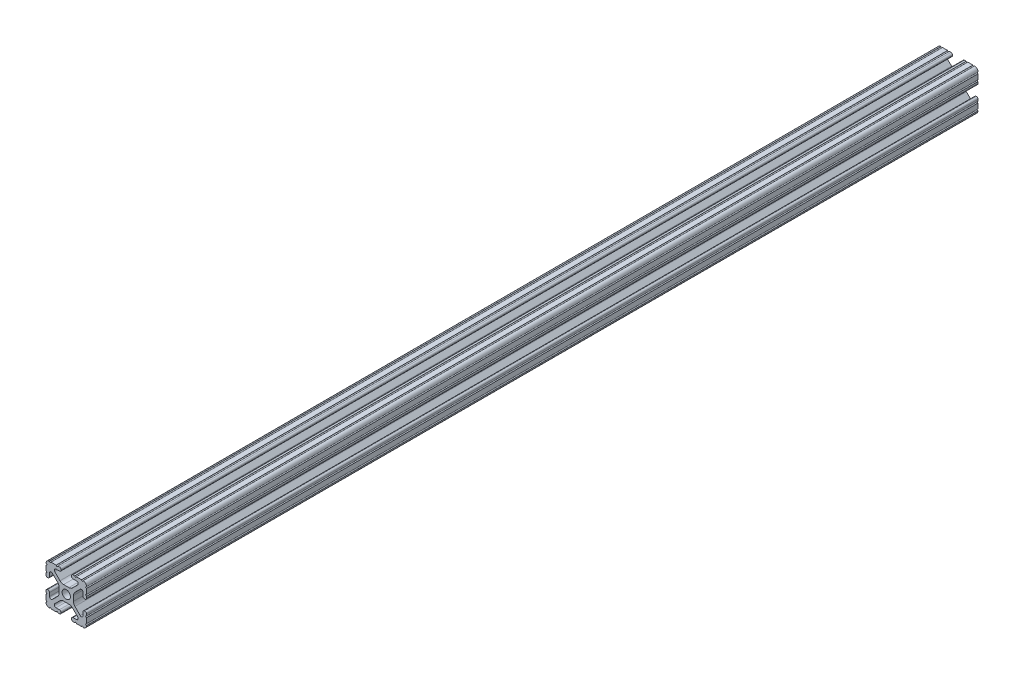
SolidWorks part; units mm, degrees
ref_plane "Front Plane" through (0, 0, 0) normal (0, 0, 1) x (1, 0, 0)
ref_plane "Top Plane" through (0, 0, 0) normal (0, 1, 0) x (1, 0, 0)
ref_plane "Right Plane" through (0, 0, 0) normal (1, 0, 0) x (0, 0, -1)
sketch "Sketch1" plane through (0, 0, 0) normal (0, 0, 1) x (1, 0, 0)
  line L88 (-7.1797, -8.6452) -> (-3.9523, -5.4237)
  line L89 (-1.7093, -4.4958) -> (1.7093, -4.4958)
  line L90 (3.9523, -5.4237) -> (7.1797, -8.6452)
  line L91 (6.4164, -10.4902) -> (4.2875, -10.4902)
  line L92 (3.2385, -11.5392) -> (3.2385, -11.651)
  line L93 (4.2875, -12.7) -> (5.3171, -12.7)
  line L94 (6.3331, -12.7) -> (9.5504, -12.7)
  line L95 (12.7, -9.5504) -> (12.7, -6.3331)
  line L96 (12.7, -5.3171) -> (12.7, -4.2875)
  line L97 (11.651, -3.2385) -> (11.5392, -3.2385)
  line L98 (10.4902, -4.2875) -> (10.4902, -6.4021)
  line L99 (8.7371, -7.1294) -> (5.441, -3.8408)
  line L100 (4.5085, -1.5932) -> (4.5085, 1.5932)
  line L101 (5.441, 3.8408) -> (8.7371, 7.1294)
  line L102 (10.4902, 6.4021) -> (10.4902, 4.2875)
  line L103 (11.5392, 3.2385) -> (11.651, 3.2385)
  line L104 (12.7, 4.2875) -> (12.7, 5.3171)
  line L105 (12.7, 6.3331) -> (12.7, 9.5504)
  line L106 (9.5504, 12.7) -> (6.3331, 12.7)
  line L107 (5.3171, 12.7) -> (4.2875, 12.7)
  line L108 (3.2385, 11.651) -> (3.2385, 11.5392)
  line L109 (4.2875, 10.4902) -> (6.4768, 10.4902)
  line L110 (7.207, 8.7244) -> (3.8983, 5.4232)
  line L111 (1.6558, 4.4958) -> (-1.6558, 4.4958)
  line L112 (-3.8983, 5.4232) -> (-7.207, 8.7244)
  line L113 (-6.4768, 10.4902) -> (-4.2875, 10.4902)
  line L114 (-3.2385, 11.5392) -> (-3.2385, 11.651)
  line L115 (-4.2875, 12.7) -> (-5.3171, 12.7)
  line L116 (-6.3331, 12.7) -> (-9.5504, 12.7)
  line L117 (-12.7, 9.5504) -> (-12.7, 6.3331)
  line L118 (-12.7, 5.3171) -> (-12.7, 4.2875)
  line L119 (-11.651, 3.2385) -> (-11.5392, 3.2385)
  line L120 (-10.4902, 4.2875) -> (-10.4902, 6.4021)
  line L121 (-8.7371, 7.1294) -> (-5.441, 3.8408)
  line L122 (-4.5085, 1.5932) -> (-4.5085, -1.5932)
  line L123 (-5.441, -3.8408) -> (-8.7371, -7.1294)
  line L124 (-10.4902, -6.4021) -> (-10.4902, -4.2875)
  line L125 (-11.5392, -3.2385) -> (-11.651, -3.2385)
  line L126 (-12.7, -4.2875) -> (-12.7, -5.3171)
  line L127 (-12.7, -6.3331) -> (-12.7, -9.5504)
  line L128 (-9.5504, -12.7) -> (-6.3331, -12.7)
  line L129 (-5.3171, -12.7) -> (-4.2875, -12.7)
  line L130 (-3.2385, -11.651) -> (-3.2385, -11.5392)
  line L131 (-4.2875, -10.4902) -> (-6.4164, -10.4902)
  circle A1 centre (0, 0) radius 2.6035
  arc A104 (-7.1797, -8.6452) -> (-6.4164, -10.4902) centre (-6.4164, -9.4098) ccw
  arc A105 (-1.7093, -4.4958) -> (-3.9523, -5.4237) centre (-1.7093, -7.6708) ccw
  arc A106 (3.9523, -5.4237) -> (1.7093, -4.4958) centre (1.7093, -7.6708) ccw
  arc A107 (6.4164, -10.4902) -> (7.1797, -8.6452) centre (6.4164, -9.4098) ccw
  arc A108 (4.2875, -10.4902) -> (3.2385, -11.5392) centre (4.2875, -11.5392) ccw
  arc A109 (3.2385, -11.651) -> (4.2875, -12.7) centre (4.2875, -11.651) ccw
  arc A110 (6.3331, -12.7) -> (5.3171, -12.7) centre (5.8251, -12.7) ccw
  arc A111 (10.5664, -12.6998) -> (9.5504, -12.7) centre (10.0584, -12.7) ccw
  arc A112 (10.5664, -12.6998) -> (12.6998, -10.5664) centre (10.5918, -10.5918) ccw
  arc A113 (12.7, -9.5504) -> (12.6998, -10.5664) centre (12.7, -10.0584) ccw
  arc A114 (12.7, -5.3171) -> (12.7, -6.3331) centre (12.7, -5.8251) ccw
  arc A115 (12.7, -4.2875) -> (11.651, -3.2385) centre (11.651, -4.2875) ccw
  arc A116 (11.5392, -3.2385) -> (10.4902, -4.2875) centre (11.5392, -4.2875) ccw
  arc A117 (8.7371, -7.1294) -> (10.4902, -6.4021) centre (9.4628, -6.4021) ccw
  arc A118 (4.5085, -1.5932) -> (5.441, -3.8408) centre (7.6835, -1.5932) ccw
  arc A119 (5.441, 3.8408) -> (4.5085, 1.5932) centre (7.6835, 1.5932) ccw
  arc A120 (10.4902, 6.4021) -> (8.7371, 7.1294) centre (9.4628, 6.4021) ccw
  arc A121 (10.4902, 4.2875) -> (11.5392, 3.2385) centre (11.5392, 4.2875) ccw
  arc A122 (11.651, 3.2385) -> (12.7, 4.2875) centre (11.651, 4.2875) ccw
  arc A123 (12.7, 6.3331) -> (12.7, 5.3171) centre (12.7, 5.8251) ccw
  arc A124 (12.6998, 10.5664) -> (12.7, 9.5504) centre (12.7, 10.0584) ccw
  arc A125 (12.6998, 10.5664) -> (10.5664, 12.6998) centre (10.5918, 10.5918) ccw
  arc A126 (9.5504, 12.7) -> (10.5664, 12.6998) centre (10.0584, 12.7) ccw
  arc A127 (5.3171, 12.7) -> (6.3331, 12.7) centre (5.8251, 12.7) ccw
  arc A128 (4.2875, 12.7) -> (3.2385, 11.651) centre (4.2875, 11.651) ccw
  arc A129 (3.2385, 11.5392) -> (4.2875, 10.4902) centre (4.2875, 11.5392) ccw
  arc A130 (7.207, 8.7244) -> (6.4768, 10.4902) centre (6.4768, 9.4563) ccw
  arc A131 (1.6558, 4.4958) -> (3.8983, 5.4232) centre (1.6558, 7.6708) ccw
  arc A132 (-3.8983, 5.4232) -> (-1.6558, 4.4958) centre (-1.6558, 7.6708) ccw
  arc A133 (-6.4768, 10.4902) -> (-7.207, 8.7244) centre (-6.4768, 9.4563) ccw
  arc A134 (-4.2875, 10.4902) -> (-3.2385, 11.5392) centre (-4.2875, 11.5392) ccw
  arc A135 (-3.2385, 11.651) -> (-4.2875, 12.7) centre (-4.2875, 11.651) ccw
  arc A136 (-6.3331, 12.7) -> (-5.3171, 12.7) centre (-5.8251, 12.7) ccw
  arc A137 (-10.5664, 12.6998) -> (-9.5504, 12.7) centre (-10.0584, 12.7) ccw
  arc A138 (-10.5664, 12.6998) -> (-12.6998, 10.5664) centre (-10.5918, 10.5918) ccw
  arc A139 (-12.7, 9.5504) -> (-12.6998, 10.5664) centre (-12.7, 10.0584) ccw
  arc A140 (-12.7, 5.3171) -> (-12.7, 6.3331) centre (-12.7, 5.8251) ccw
  arc A141 (-12.7, 4.2875) -> (-11.651, 3.2385) centre (-11.651, 4.2875) ccw
  arc A142 (-11.5392, 3.2385) -> (-10.4902, 4.2875) centre (-11.5392, 4.2875) ccw
  arc A143 (-8.7371, 7.1294) -> (-10.4902, 6.4021) centre (-9.4628, 6.4021) ccw
  arc A144 (-4.5085, 1.5932) -> (-5.441, 3.8408) centre (-7.6835, 1.5932) ccw
  arc A145 (-5.441, -3.8408) -> (-4.5085, -1.5932) centre (-7.6835, -1.5932) ccw
  arc A146 (-10.4902, -6.4021) -> (-8.7371, -7.1294) centre (-9.4628, -6.4021) ccw
  arc A147 (-10.4902, -4.2875) -> (-11.5392, -3.2385) centre (-11.5392, -4.2875) ccw
  arc A148 (-11.651, -3.2385) -> (-12.7, -4.2875) centre (-11.651, -4.2875) ccw
  arc A149 (-12.7, -6.3331) -> (-12.7, -5.3171) centre (-12.7, -5.8251) ccw
  arc A150 (-12.6998, -10.5664) -> (-12.7, -9.5504) centre (-12.7, -10.0584) ccw
  arc A151 (-12.6998, -10.5664) -> (-10.5664, -12.6998) centre (-10.5918, -10.5918) ccw
  arc A152 (-9.5504, -12.7) -> (-10.5664, -12.6998) centre (-10.0584, -12.7) ccw
  arc A153 (-5.3171, -12.7) -> (-6.3331, -12.7) centre (-5.8251, -12.7) ccw
  arc A154 (-4.2875, -12.7) -> (-3.2385, -11.651) centre (-4.2875, -11.651) ccw
  arc A155 (-3.2385, -11.5392) -> (-4.2875, -10.4902) centre (-4.2875, -11.5392) ccw
extrude "Boss-Extrude1" add sketch "Sketch1" along normal mid plane 558.8
sketch "Sketch2" plane through (0, 4.4958, 0) normal (0, 1, 0) x (1, 0, 0)
  line L0 (1.6558, 279.4) -> (-1.6558, 279.4) construction
  line L1 (1.6558, -279.4) -> (-1.6558, -279.4) construction
  circle A0 centre (0.2407, 228.6) radius 3.175
  circle A1 centre (0, -228.6) radius 3.175
  dimension "D1" = 6.35
  dimension "D2" = 50.8
  dimension "D3" = 6.35
  dimension "D4" = 50.8
extrude "Cut-Extrude1" cut sketch "Sketch2" against normal through all contours A1 | A0
extrude "Cut-Extrude2" cut sketch "Sketch2<3>" against normal blind 2.54 and the other way through all
sketch "Sketch2<3>" plane through (0, 4.4958, 0) normal (0, 1, 0) x (1, 0, 0) same geometry as "Sketch2"
